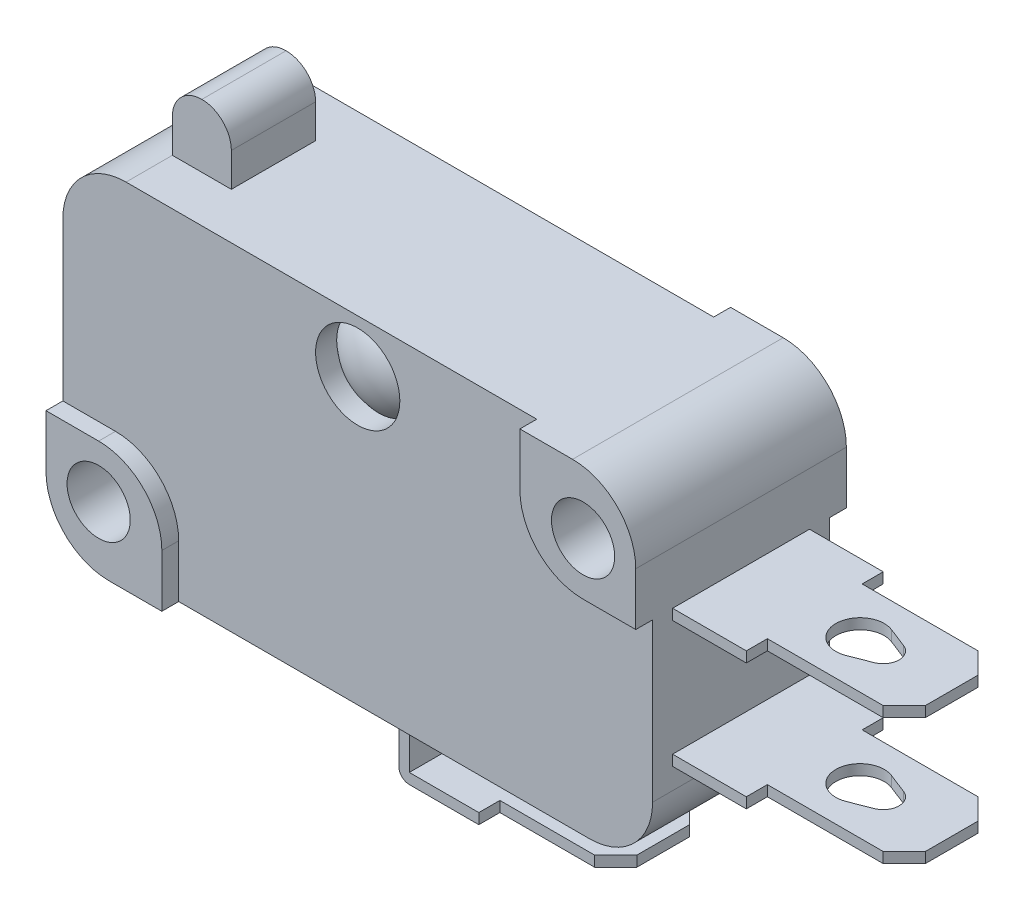
SolidWorks part; units mm, degrees
ref_plane "前基準面" through (0, 0, 0) normal (0, 0, 1) x (1, 0, 0)
ref_plane "上基準面" through (0, 0, 0) normal (0, 1, 0) x (1, 0, 0)
ref_plane "右基準面" through (0, 0, 0) normal (1, 0, 0) x (0, 0, -1)
sketch "草圖1" plane through (0, 0, 0) normal (0, 0, 1) x (1, 0, 0)
  line L0 (0, 8) -> (0, -8) construction
  line L1 (-14, 8) -> (14, 8)
  line L2 (-14, 8) -> (-14, -8)
  line L3 (-14, -8) -> (14, -8)
  line L4 (14, 8) -> (14, -8)
  dimension "D1" = 28
  dimension "D2" = 16
extrude "伸長1" add sketch "草圖1" along normal mid plane 10
fillet "圓角1" radius 3 4 edges at (-14, -8, 0) (-14, 8, 0) (14, -8, 0) (14, 8, 0)
sketch "草圖2" plane through (0, 0, 5) normal (0, 0, 1) x (1, 0, 0)
  line L0 (-14, -2.5) -> (-8.5, -2.5)
  line L1 (-14, 5) -> (-14, -5) construction
  line L2 (-8.5, -2.5) -> (-8.5, -8)
  line L3 (-11, -8) -> (11, -8) construction
  line L4 (11, 8) -> (-11, 8) construction
  line L5 (14, -5) -> (14, 5) construction
  line L6 (-14, 5) -> (-14, -2.5)
  line L7 (8.5, 8) -> (-11, 8)
  line L8 (14, -5) -> (14, 2.5)
  line L9 (-8.5, -8) -> (11, -8)
  line L10 (8.5, 8) -> (8.5, 2.5)
  line L11 (8.5, 2.5) -> (14, 2.5)
  arc A0 (-11, 8) -> (-14, 5) centre (-11, 5) ccw construction
  arc A2 (11, -8) -> (14, -5) centre (11, -5) ccw construction
  arc A3 (-11, 8) -> (-14, 5) centre (-11, 5) ccw
  arc A5 (11, -8) -> (14, -5) centre (11, -5) ccw
  dimension "D1" = 17
  dimension "D2" = 5.5
extrude "伸長2" cut sketch "草圖2" against normal blind 0.8
fillet "圓角2" radius 3 2 edges at (-8.5, -2.5, 4.6) (8.5, 2.5, 4.6)
mirror "鏡射1" about plane through (0, 0, 0) normal (0, 0, 1) of "圓角2", "伸長2"
sketch "草圖3" plane through (0, 0, -5) normal (0, 0, -1) x (-1, 0, 0)
  circle A0 centre (-11.5, 5) radius 1.5
  circle A1 centre (11.5, -5) radius 1.5
  dimension "D1" = 3
  dimension "D2" = 23
  dimension "D3" = 11.5
  dimension "D4" = 10
  dimension "D5" = 5
extrude "伸長3" cut sketch "草圖3" against normal through all
sketch "草圖4" plane through (0, 0, -4.2) normal (0, 0, -1) x (-1, 0, 0)
  line L0 (-8.5, 8) -> (11, 8) construction
  circle A0 centre (0, 5.5) radius 2
  dimension "D1" = 4
  dimension "D2" = 2.5
extrude "伸長4" cut sketch "草圖4" against normal blind 0.5
sketch "草圖5" plane through (0, 0, 4.2) normal (0, 0, 1) x (1, 0, 0)
  circle A0 centre (0, 5.5) radius 2 construction
  circle A1 centre (0, 5.5) radius 2
extrude "伸長5" cut sketch "草圖5" against normal blind 1
ref_plane "平面1" through (0, 5.5, 0) normal (0, 1, 0) x (-1, 0, 0)
sketch "草圖9" plane through (0, 5.5, 0) normal (0, 1, 0) x (-1, 0, 0)
  line L0 (0, 3.2) -> (2, 3.2)
  line L1 (0, 3.2) -> (0, 4)
  line L2 (2, 3.2) -> (-2, 3.2) construction
  line L3 (2, 4.2) -> (-2, 4.2) construction
  arc A0 (2, 3.2) -> (0, 4) centre (0, 1.1) ccw
  dimension "D1" = 0.2
revolve "旋轉1" add sketch "草圖9" angle 360 about L1
sketch "草圖10" plane through (14, 0, 0) normal (1, 0, 0) x (0, 0, -1)
  line L0 (4.2, -8) -> (-4.2, -8) construction
  line L1 (-3.25, -3.5) -> (3.25, -3.5)
  line L2 (-3.25, -3.5) -> (-3.25, -4)
  line L3 (-3.25, -4) -> (3.25, -4)
  line L4 (3.25, -3.5) -> (3.25, -4)
  line L5 (-3.25, 2.5) -> (3.25, 2.5)
  line L6 (-3.25, 2.5) -> (-3.25, 2)
  line L7 (-3.25, 2) -> (3.25, 2)
  line L8 (3.25, 2.5) -> (3.25, 2)
  line L9 (0, 2.5) -> (0, 2) construction
  dimension "D1" = 0.5
  dimension "D2" = 6.5
  dimension "D3" = 4
  dimension "D4" = 6.5
extrude "伸長9" add sketch "草圖10" along normal blind 10
sketch "草圖11" plane through (0, 2.5, 0) normal (0, 1, 0) x (1, 0, 0)
  line L0 (20.0682, 1.0713) -> (21.0227, 0.6987)
  line L1 (24, 3.25) -> (17.5, 3.25)
  line L2 (24, 3.25) -> (24, 2.25)
  line L3 (24, 2.25) -> (17.5, 2.25)
  line L4 (17.5, 3.25) -> (17.5, 2.25)
  line L5 (24, -3.25) -> (17.5, -3.25)
  line L6 (24, -3.25) -> (24, -2.25)
  line L7 (24, -2.25) -> (17.5, -2.25)
  line L8 (17.5, -3.25) -> (17.5, -2.25)
  line L9 (20.0682, -1.0713) -> (21.0227, -0.6987)
  line L10 (18.5, 0) -> (21.5, 0) construction
  line L11 (24, 3.25) -> (24, -3.25) construction
  arc A0 (20.0682, 1.0713) -> (20.0682, -1.0713) centre (19.65, 0) ccw
  arc A1 (21.0227, -0.6987) -> (21.0227, 0.6987) centre (20.75, 0) ccw
  dimension "D3" = 1.15
  dimension "D4" = 0.75
  dimension "D1" = 4.5
  dimension "D2" = 6.5
  dimension "D5" = 3
  dimension "D6" = 2.5
extrude "伸長10" cut sketch "草圖11" against normal through all
chamfer "導角1" distance 1 angle 45 4 edges at (24, -3.75, -2.25) (24, 2.25, -2.25) (24, -3.75, 2.25) (24, 2.25, 2.25)
sketch "草圖12" plane through (0, 0, 0) normal (0, 0, 1) x (1, 0, 0)
  line L0 (1, -8) -> (1.5, -8)
  line L1 (-8.5, -8) -> (11, -8) construction
  line L2 (1.5, -8) -> (1.5, -10.5)
  line L3 (1.5, -10.5) -> (10.3, -10.5)
  line L4 (10.3, -10.5) -> (10.3, -11)
  line L5 (10.3, -11) -> (1, -11)
  line L6 (1, -11) -> (1, -8)
  line L7 (-14, 5) -> (-14, -2.5) construction
  dimension "D1" = 0.5
  dimension "D2" = 0.5
  dimension "D3" = 15
  dimension "D4" = 3
  dimension "D5" = 9.3
extrude "伸長11" add sketch "草圖12" along normal mid plane 6.5
fillet "圓角7" radius 0.5 1 edges at (1, -11, 0)
sketch "草圖13" plane through (0, -11, 0) normal (0, -1, 0) x (1, 0, 0)
  line L0 (23, 2.25) -> (17.5, 2.25) construction
  line L1 (10.3, 3.25) -> (4.8, 3.25)
  line L2 (10.3, 3.25) -> (10.3, 2.25)
  line L3 (10.3, 2.25) -> (4.8, 2.25)
  line L4 (4.8, 3.25) -> (4.8, 2.25)
  line L5 (10.3, -3.25) -> (4.8, -3.25)
  line L6 (10.3, -3.25) -> (10.3, -2.25)
  line L7 (10.3, -2.25) -> (4.8, -2.25)
  line L8 (4.8, -3.25) -> (4.8, -2.25)
  line L9 (6.3682, 1.0713) -> (7.3227, 0.6987)
  line L10 (6.3682, -1.0713) -> (7.3227, -0.6987)
  line L11 (21.0227, 0.6987) -> (20.0682, 1.0713) construction
  line L12 (10.3, 3.25) -> (10.3, -3.25) construction
  arc A0 (6.3682, 1.0713) -> (6.3682, -1.0713) centre (5.95, 0) ccw
  arc A1 (7.3227, -0.6987) -> (7.3227, 0.6987) centre (7.05, 0) ccw
  arc A2 (21.0227, -0.6987) -> (21.0227, 0.6987) centre (20.75, 0) ccw construction
  arc A3 (20.0682, 1.0713) -> (20.0682, -1.0713) centre (19.65, 0) ccw construction
  dimension "D1" = 3.25
extrude "伸長12" cut sketch "草圖13" against normal up to surface (3 mm away) up to face at (-4.25, -8, 0)
chamfer "導角2" distance 1 angle 45 2 edges at (10.3, -10.75, -2.25) (10.3, -10.75, 2.25)
sketch "草圖14" plane through (0, 8, 0) normal (0, 1, 0) x (1, 0, 0)
  line L0 (-11, 0) -> (-8.2, 0) construction
  line L1 (-11, 2) -> (-8.2, 2)
  line L2 (-11, 2) -> (-11, -2)
  line L3 (-11, -2) -> (-8.2, -2)
  line L4 (-8.2, 2) -> (-8.2, -2)
  line L5 (-14, -4.2) -> (-14, 4.2) construction
  dimension "D1" = 2.8
  dimension "D2" = 4
  dimension "D3" = 3
extrude "伸長13" add sketch "草圖14" along normal blind 3
fillet "圓角8" radius 1.4 2 edges at (-8.2, 11, 0) (-11, 11, 0)
